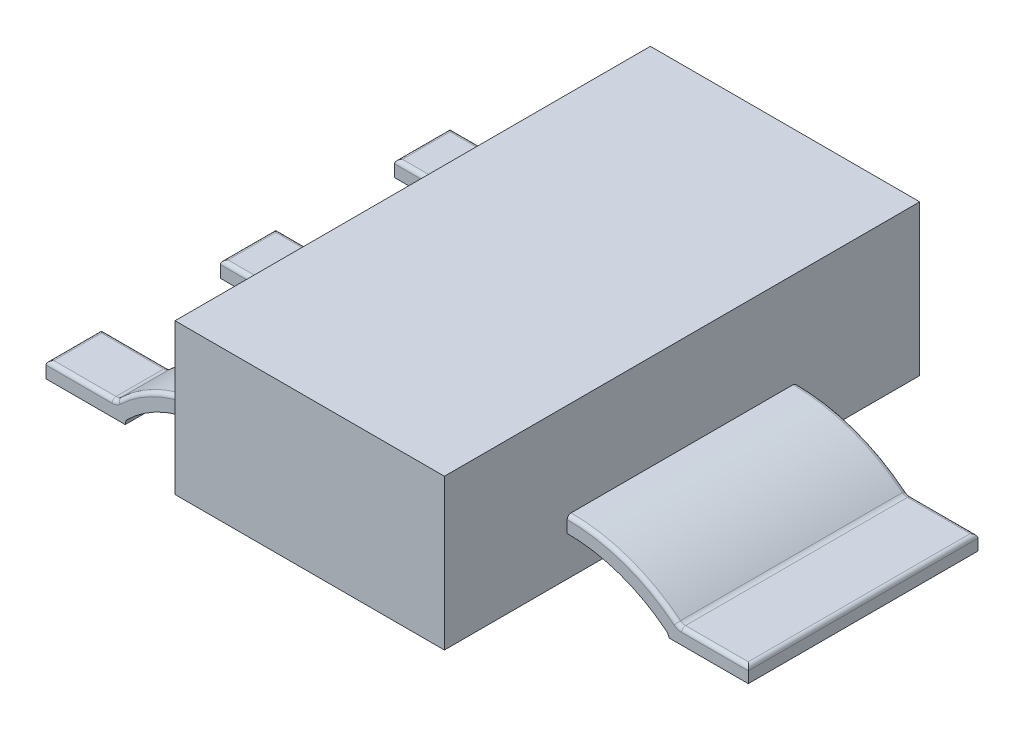
SolidWorks part; units mm, degrees
ref_plane "Plan de face" through (0, 0, 0) normal (0, 0, 1) x (1, 0, 0)
ref_plane "Plan de dessus" through (0, 0, 0) normal (0, 1, 0) x (1, 0, 0)
ref_plane "Plan de droite" through (0, 0, 0) normal (1, 0, 0) x (0, 0, -1)
sketch "Esquisse1" plane through (0, 0, 0) normal (0, 1, 0) x (1, 0, 0)
  line L1 (0, 0) -> (3.4, 0)
  line L2 (0, 0) -> (0, 6)
  line L3 (0, 6) -> (3.4, 6)
  line L4 (3.4, 0) -> (3.4, 6)
  dimension "D1" = 6
  dimension "D2" = 3.4
extrude "Boss.-Extru.1" add sketch "Esquisse1" along normal blind 1.9
sketch "Esquisse2" plane through (3.4, 0, 0) normal (1, 0, 0) x (0, 0, -1)
  line L0 (3, 1.9) -> (3, 0) construction
  line L1 (1.55, 0.6998) -> (4.45, 0.6998)
  line L2 (1.55, 0.6998) -> (1.55, 0.4998)
  line L3 (1.55, 0.4998) -> (4.45, 0.4998)
  line L4 (4.45, 0.6998) -> (4.45, 0.4998)
  line L5 (0, 1.9) -> (6, 1.9) construction
  line L6 (0, 0) -> (6, 0) construction
  line L7 (3, 0.6998) -> (3, 0.4998) construction
  line L8 (1.55, -1.5002) -> (4.45, -1.5002) construction
  dimension "D1" = 0.2
  dimension "D2" = 2.9
  dimension "D3" = 2
revolve "Révolution1" add sketch "Esquisse2" angle 40 about L8
sketch "Esquisse4" plane through (0, 0, 0) normal (0, 1, 0) x (1, 0, 0)
  line L1 (4.6856, 1.55) -> (5.6856, 1.55)
  line L2 (4.6856, 1.55) -> (4.6856, 4.45)
  line L3 (4.6856, 4.45) -> (5.6856, 4.45)
  line L4 (5.6856, 1.55) -> (5.6856, 4.45)
  dimension "D1" = 2.9
  dimension "D2" = 1
extrude "Boss.-Extru.2" add sketch "Esquisse4" along normal blind 0.19
fillet "Congé1" radius 0.1 2 edges at (4.6856, 0.0319, -3) (4.8083, 0.19, -3)
fillet "Congé2" radius 0.05 7 edges at (4.1324, 0.5743, -1.55) (4.8107, 0.1957, -1.55) (4.1324, 0.5743, -4.45) (4.8107, 0.1957, -4.45) (5.2648, 0.19, -1.55) (5.2648, 0.19, -4.45) (5.6856, 0.19, -3)
sketch "Esquisse6" plane through (0, 0, 0) normal (-1, 0, 0) x (0, 0, 1)
  line L0 (-6, 0.4998) -> (0, 0.4998) construction
  line L1 (-6, 1.9) -> (-6, 0) construction
  line L2 (0, 1.9) -> (0, 0) construction
  line L4 (-4.1, 0.4998) -> (-4.1, 0) construction
  line L5 (-3.35, 0.4998) -> (-2.65, 0.4998)
  line L6 (-3.35, 0.4998) -> (-3.35, 0.6998)
  line L7 (-3.35, 0.6998) -> (-2.65, 0.6998)
  line L8 (-2.65, 0.4998) -> (-2.65, 0.6998)
  line L9 (-1.9, 0.4998) -> (-1.9, 0) construction
  line L10 (-5.55, 0.4998) -> (-5.55, 0.6998)
  line L11 (-4.85, 0.4998) -> (-5.55, 0.4998)
  line L12 (-3, 0.5) -> (-3, 0) construction
  line L13 (-6, 0) -> (0, 0) construction
  line L14 (-4.85, 0.6998) -> (-5.55, 0.6998)
  line L15 (-4.85, 0.4998) -> (-4.85, 0.6998)
  line L16 (-1.15, 0.4998) -> (-1.15, 0.6998)
  line L17 (-0.45, 0.4998) -> (-1.15, 0.4998)
  line L18 (-0.45, 0.6998) -> (-1.15, 0.6998)
  line L19 (-0.45, 0.4998) -> (-0.45, 0.6998)
  line L20 (-6, -1) -> (0, -1) construction
  point P14 (-3, 0.4998)
  dimension "D2" = 0.2
  dimension "D1" = 0.5
  dimension "D3" = 0.7
  dimension "D4" = 1.1
  dimension "D5" = 1.1
  dimension "D6" = 1
revolve "Révolution2" add sketch "Esquisse6" angle 46 about L20 other way angle 46
sketch "Esquisse8" plane through (0, 0, 0) normal (0, 1, 0) x (1, 0, 0)
  line L1 (-1.0789, 0.45) -> (-2.0789, 0.45)
  line L2 (-1.0789, 0.45) -> (-1.0789, 1.15)
  line L3 (-1.0789, 1.15) -> (-2.0789, 1.15)
  line L4 (-2.0789, 0.45) -> (-2.0789, 1.15)
  line L5 (-1.0789, 2.65) -> (-2.0789, 2.65)
  line L6 (-1.0789, 2.65) -> (-1.0789, 3.35)
  line L7 (-1.0789, 3.35) -> (-2.0789, 3.35)
  line L8 (-2.0789, 2.65) -> (-2.0789, 3.35)
  line L9 (-1.0789, 4.85) -> (-2.0789, 4.85)
  line L10 (-1.0789, 4.85) -> (-1.0789, 5.55)
  line L11 (-1.0789, 5.55) -> (-2.0789, 5.55)
  line L12 (-2.0789, 4.85) -> (-2.0789, 5.55)
  dimension "D1" = 1
  dimension "D2" = 1
  dimension "D3" = 1
extrude "Boss.-Extru.3" add sketch "Esquisse8" along normal blind 0.2
fillet "Congé3" radius 0.1 6 edges at (-1.0789, 0.0419, -5.2) (-1.0789, 0.0419, -3) (-1.0789, 0.0419, -0.8) (-1.2039, 0.2, -0.8) (-1.2039, 0.2, -5.2) (-1.2039, 0.2, -3)
fillet "Congé4" radius 0.05 21 edges at (-0.6334, 0.5774, -5.55) (-1.2075, 0.2072, -5.55) (-0.6334, 0.5774, -4.85) (-1.2075, 0.2072, -4.85) (-0.6334, 0.5774, -1.15) (-1.2075, 0.2072, -1.15) (-0.6334, 0.5774, -0.45) (-1.2075, 0.2072, -0.45) (-0.6334, 0.5774, -3.35) (-1.2075, 0.2072, -3.35) (-0.6334, 0.5774, -2.65) (-1.2075, 0.2072, -2.65) (-2.0789, 0.2, -5.2) (-1.6618, 0.2, -5.55) (-1.6618, 0.2, -4.85) (-2.0789, 0.2, -0.8) (-1.6618, 0.2, -1.15) (-1.6618, 0.2, -0.45) (-2.0789, 0.2, -3) (-1.6618, 0.2, -3.35) (-1.6618, 0.2, -2.65)
